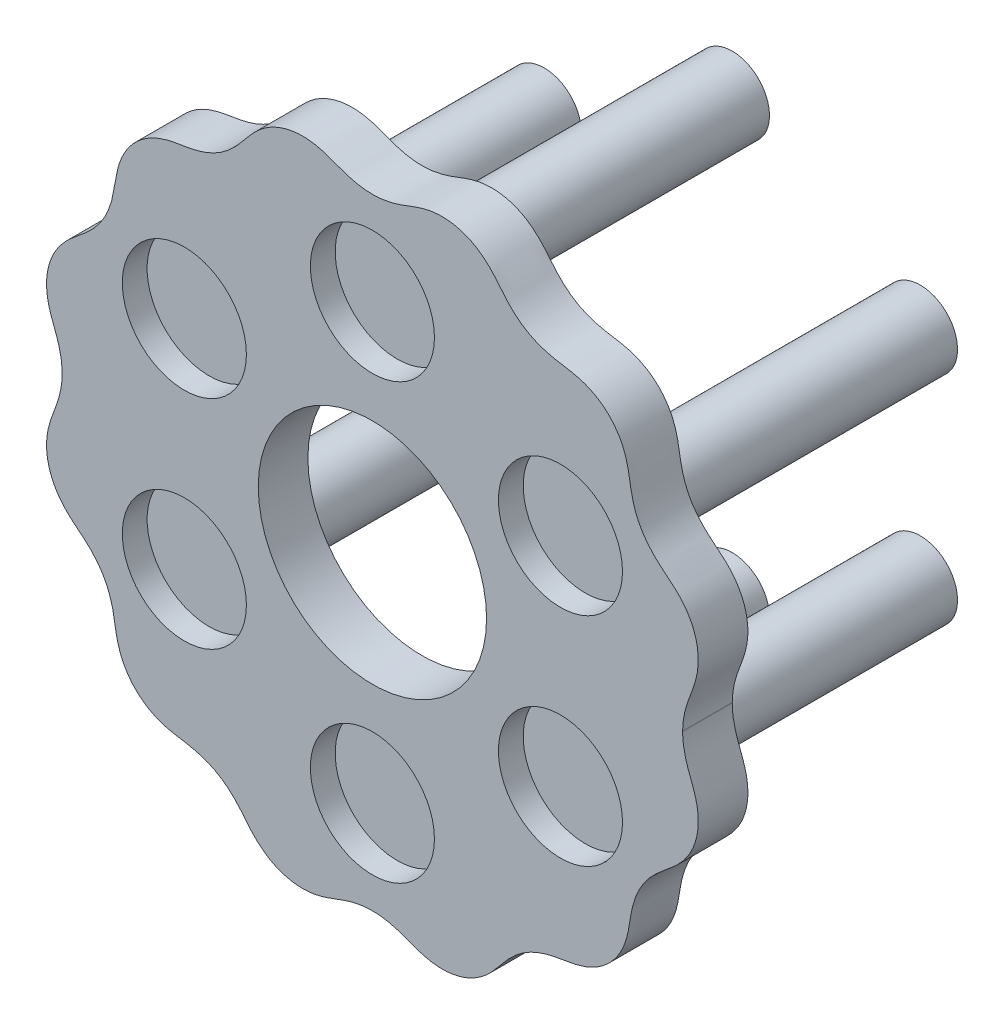
SolidWorks part; units mm, degrees
material "Polylactic Acid (PLA)"
ref_plane "Front Plane" through (0, 0, 0) normal (0, 0, 1) x (1, 0, 0)
ref_plane "Top Plane" through (0, 0, 0) normal (0, 1, 0) x (1, 0, 0)
ref_plane "Right Plane" through (0, 0, 0) normal (1, 0, 0) x (0, 0, -1)
sketch "Sketch3" plane through (0, 0, 0) normal (0, 0, 1) x (1, 0, 0)
  circle A0 centre (0, 0) radius 9.2
  circle A1 centre (0, 0) radius 17.5 construction
  circle A2 centre (0, 17.5) radius 5 construction
  circle A3 centre (15.1554, 8.75) radius 5 construction
  circle A4 centre (15.1554, -8.75) radius 5 construction
  circle A5 centre (0, -17.5) radius 5 construction
  circle A6 centre (-15.1554, -8.75) radius 5 construction
  circle A7 centre (-15.1554, 8.75) radius 5 construction
  spline S0 degree 4 poles (21.1908, 13.4898) (21.2856, 13.2293) (21.5047, 12.7166) (21.9256, 11.9944) (22.6531, 11.1441) (23.6487, 10.2926) (24.8547, 9.373) (25.8136, 8.0448) (26.2513, 6.5807) (26.291, 5.362) (26.1425, 4.3728) (25.9222, 3.637) (25.662, 2.971) (25.4535, 2.4089) (25.3271, 2.03) (25.2348, 1.7101) (25.1694, 1.4518) (25.1138, 1.1915) (25.0684, 0.9287) (25.0339, 0.6638) (25.0136, 0.4392) (25.0034, 0.2182) (24.9998, 0.0511) (24.9998, -0.0519) (25.0027, -0.1861) (25.0086, -0.3317) (25.0175, -0.4711) (25.0292, -0.6041) (25.0438, -0.7358) (25.0613, -0.8682) (25.0866, -1.0342) (25.1223, -1.2324) (25.1717, -1.4616) (25.2379, -1.7216) (25.3315, -2.0435) (25.4377, -2.3615) (25.5528, -2.6764) (25.6953, -3.0525) (25.8373, -3.4288) (26.0075, -3.9196) (26.1691, -4.5364) (26.293, -5.4006) (26.2489, -6.5093) (25.9006, -7.7589) (25.2509, -8.824) (24.5594, -9.5488) (23.8729, -10.1329) (23.242, -10.6335) (22.5405, -11.262) (21.8598, -12.0935) (21.3371, -13.0271) (20.9865, -14.0322) (20.7832, -15.0691) (20.6292, -16.2106) (20.2958, -17.4236) (19.6201, -18.6144) (18.5782, -19.6482) (17.3773, -20.3163) (16.1515, -20.64) (14.7399, -20.8265) (13.4394, -21.1259) (12.2371, -21.7311) (11.2173, -22.5863) (10.5105, -23.3824) (9.8039, -24.3012) (8.9125, -25.2023) (7.7314, -25.9117) (6.3093, -26.2999) (4.9316, -26.2885) (3.7061, -25.9646) (2.6337, -25.523) (1.6267, -25.1818) (0.5814, -24.9891) (-0.4789, -24.9807) (-1.521, -25.1546) (-2.5204, -25.4795) (-3.4192, -25.8479) (-4.2744, -26.1194) (-5.0841, -26.2552) (-5.8272, -26.2778) (-6.7511, -26.1767) (-7.8194, -25.8504) (-8.8645, -25.242) (-9.7745, -24.3376) (-10.489, -23.4094) (-11.1981, -22.6045) (-12.0193, -21.9108) (-12.9507, -21.3713) (-13.9612, -21.0044) (-15.0125, -20.7907) (-16.1735, -20.6366) (-17.4128, -20.3041) (-18.6216, -19.6172) (-19.5352, -18.6909) (-20.1095, -17.7445) (-20.4683, -16.8114) (-20.6693, -15.9295) (-20.8004, -14.9513) (-21.0215, -13.8975) (-21.3995, -12.8918) (-21.9457, -11.9715) (-22.6396, -11.1645) (-23.4354, -10.4692) (-24.3471, -9.7654) (-25.2322, -8.8715) (-25.9257, -7.6947) (-26.3017, -6.2829) (-26.2854, -4.917) (-25.9623, -3.7014) (-25.5242, -2.6362) (-25.1845, -1.6355) (-24.9896, -0.5891) (-24.9797, 0.481) (-25.1578, 1.5405) (-25.4952, 2.5629) (-25.8707, 3.4757) (-26.1355, 4.3406) (-26.2885, 5.3286) (-26.2611, 6.43) (-25.9336, 7.6784) (-25.2377, 8.8666) (-24.345, 9.7676) (-23.427, 10.4756) (-22.627, 11.1764) (-21.9369, 11.9843) (-21.3977, 12.8977) (-21.0267, 13.8865) (-20.8061, 14.9146) (-20.653, 16.0603) (-20.3956, 17.1161) (-19.9569, 18.0284) (-19.3001, 18.9288) (-18.4837, 19.6923) (-17.4358, 20.2946) (-16.1976, 20.6324) (-15.0368, 20.7873) (-13.9849, 20.9979) (-12.9731, 21.361) (-12.0395, 21.8966) (-11.2157, 22.5872) (-10.504, 23.3902) (-9.7903, 24.3186) (-8.8841, 25.2269) (-7.6859, 25.9322) (-6.4273, 26.2622) (-5.3206, 26.2881) (-4.3329, 26.1336) (-3.4683, 25.8679) (-2.5556, 25.4923) (-1.5328, 25.1559) (-0.4731, 24.979) (0.597, 24.9904) (1.6431, 25.1866) (2.6435, 25.5272) (3.7088, 25.9651) (4.9249, 26.2864) (6.2909, 26.3007) (7.702, 25.9226) (8.8779, 25.2273) (9.7704, 24.341) (10.4741, 23.4292) (11.1701, 22.634) (11.978, 21.941) (12.899, 21.3961) (13.9051, 21.0193) (14.9591, 20.7992) (15.9373, 20.6681) (16.819, 20.466) (17.7516, 20.1059) (18.6971, 19.5302) (19.6221, 18.6152) (20.3072, 17.4054) (20.6379, 16.1657) (20.7918, 15.0047) (21.0066, 13.9535) (21.3747, 12.9435) (21.9154, 12.0128) (22.6101, 11.1925) (23.4156, 10.4841) (24.3437, 9.7696) (25.2468, 8.858) (25.9409, 7.6621) (26.2625, 6.4138) (26.2848, 5.4123) (26.1914, 4.7043) (26.0881, 4.2266) (25.9672, 3.8023) (25.8079, 3.3457) (25.6196, 2.8553) (25.4588, 2.4245) (25.3339, 2.0507) (25.2417, 1.7354) (25.1764, 1.4809) (25.1203, 1.2244) (25.0741, 0.9651) (25.0385, 0.7047) (25.017, 0.4825) (25.0053, 0.2643) (25.0004, 0.1004) (24.9996, -0.0012) (25.0018, -0.1656) (25.01, -0.3844) (25.028, -0.6072) (25.0597, -0.8689) (25.1021, -1.1294) (25.1679, -1.4517) (25.266, -1.8346) (25.4047, -2.2742) (25.5863, -2.7686) (25.7756, -3.26) (25.9402, -3.7196) (26.0686, -4.1508) (26.1813, -4.6424) (26.2599, -5.1966) (26.2771, -5.8503) (26.1868, -6.6388) (25.9656, -7.4497) (25.5952, -8.2566) (25.0637, -9.0243) (24.3767, -9.7304) (23.5662, -10.3704) (22.7327, -11.0654) (21.9759, -11.9212) (21.5356, -12.6558) (21.307, -13.1772) (21.208, -13.4432) knots 0 0 0 0 0 0.005467 0.010935 0.016402 0.021869 0.031276 0.040682 0.047884 0.051484 0.055085 0.060328 0.062949 0.065571 0.066882 0.068192 0.069503 0.070814 0.072125 0.073435 0.074746 0.075401 0.076057 0.076717 0.077377 0.078036 0.078696 0.079356 0.080016 0.080676 0.081336 0.082656 0.083975 0.085295 0.086615 0.089254 0.090574 0.091894 0.094534 0.097173 0.100798 0.104424 0.111675 0.118848 0.126022 0.128665 0.131308 0.136594 0.14188 0.147166 0.152358 0.157549 0.16274 0.167931 0.175042 0.182153 0.189327 0.1965 0.201723 0.206946 0.217392 0.222615 0.227838 0.233061 0.238284 0.245457 0.252631 0.259805 0.266978 0.272201 0.277424 0.282647 0.287869 0.29303 0.29819 0.30335 0.30851 0.31216 0.31581 0.319459 0.323109 0.330383 0.337658 0.342925 0.348192 0.35346 0.358727 0.363994 0.369262 0.374529 0.379796 0.387071 0.394345 0.401519 0.405106 0.408692 0.413978 0.419265 0.424551 0.429837 0.435028 0.440219 0.44541 0.450602 0.457712 0.464823 0.471934 0.479045 0.484236 0.489427 0.494619 0.49981 0.505096 0.510382 0.515668 0.520954 0.524541 0.528128 0.535301 0.542475 0.549649 0.554872 0.560094 0.565317 0.57054 0.5757 0.58086 0.58602 0.591181 0.59848 0.60213 0.605779 0.613054 0.620328 0.625595 0.630863 0.63613 0.641397 0.646665 0.651932 0.657199 0.662467 0.669741 0.677015 0.684189 0.687776 0.691363 0.696649 0.701935 0.707221 0.712507 0.717698 0.722889 0.728081 0.733272 0.740383 0.747494 0.754604 0.761715 0.766906 0.772098 0.777289 0.78248 0.787766 0.793052 0.798338 0.803624 0.807211 0.810798 0.817972 0.825246 0.83252 0.837788 0.843055 0.848322 0.85359 0.858857 0.864124 0.869392 0.874659 0.881933 0.889208 0.896232 0.899744 0.9015 0.903256 0.905842 0.908428 0.911014 0.9136 0.914893 0.916186 0.917479 0.918772 0.920065 0.921358 0.922651 0.923297 0.923944 0.924592 0.92524 0.926536 0.927831 0.929127 0.930423 0.931719 0.934311 0.936903 0.939495 0.942087 0.944679 0.946512 0.948345 0.952012 0.955678 0.959345 0.963918 0.968492 0.973065 0.977639 0.983229 0.988819 0.99441 1 1 1 1 1 construction
  spline S1 degree 4 poles (25, 0) (25, -0.0284) (25.0005, -0.0852) (25.0027, -0.1861) (25.0086, -0.3317) (25.0175, -0.4711) (25.0292, -0.6041) (25.0438, -0.7358) (25.0613, -0.8682) (25.0866, -1.0342) (25.1223, -1.2324) (25.1717, -1.4616) (25.2379, -1.7216) (25.3315, -2.0435) (25.4377, -2.3615) (25.5528, -2.6764) (25.6953, -3.0525) (25.8373, -3.4288) (26.0075, -3.9196) (26.1691, -4.5364) (26.293, -5.4006) (26.2489, -6.5093) (25.9006, -7.7589) (25.2509, -8.824) (24.5594, -9.5488) (23.8729, -10.1329) (23.242, -10.6335) (22.5405, -11.262) (21.8598, -12.0935) (21.3371, -13.0271) (20.9865, -14.0322) (20.7832, -15.0691) (20.6292, -16.2106) (20.2958, -17.4236) (19.6201, -18.6144) (18.5782, -19.6482) (17.3773, -20.3163) (16.1515, -20.64) (14.7399, -20.8265) (13.4394, -21.1259) (12.2371, -21.7311) (11.2173, -22.5863) (10.5105, -23.3824) (9.8039, -24.3012) (8.9125, -25.2023) (7.7314, -25.9117) (6.3093, -26.2999) (4.9316, -26.2885) (3.7061, -25.9646) (2.6337, -25.523) (1.6267, -25.1818) (0.5814, -24.9891) (-0.4789, -24.9807) (-1.521, -25.1546) (-2.5204, -25.4795) (-3.4192, -25.8479) (-4.2744, -26.1194) (-5.0841, -26.2552) (-5.8272, -26.2778) (-6.7511, -26.1767) (-7.8194, -25.8504) (-8.8645, -25.242) (-9.7745, -24.3376) (-10.489, -23.4094) (-11.1981, -22.6045) (-12.0193, -21.9108) (-12.9507, -21.3713) (-13.9612, -21.0044) (-15.0125, -20.7907) (-16.1735, -20.6366) (-17.4128, -20.3041) (-18.6216, -19.6172) (-19.5352, -18.6909) (-20.1095, -17.7445) (-20.4683, -16.8114) (-20.6693, -15.9295) (-20.8004, -14.9513) (-21.0215, -13.8975) (-21.3995, -12.8918) (-21.9457, -11.9715) (-22.6396, -11.1645) (-23.4354, -10.4692) (-24.3471, -9.7654) (-25.2322, -8.8715) (-25.9257, -7.6947) (-26.3017, -6.2829) (-26.2854, -4.917) (-25.9623, -3.7014) (-25.5242, -2.6362) (-25.1845, -1.6355) (-24.9896, -0.5891) (-24.9797, 0.481) (-25.1578, 1.5405) (-25.4952, 2.5629) (-25.8707, 3.4757) (-26.1355, 4.3406) (-26.2885, 5.3286) (-26.2611, 6.43) (-25.9336, 7.6784) (-25.2377, 8.8666) (-24.345, 9.7676) (-23.427, 10.4756) (-22.627, 11.1764) (-21.9369, 11.9843) (-21.3977, 12.8977) (-21.0267, 13.8865) (-20.8061, 14.9146) (-20.653, 16.0603) (-20.3956, 17.1161) (-19.9569, 18.0284) (-19.3001, 18.9288) (-18.4837, 19.6923) (-17.4358, 20.2946) (-16.1976, 20.6324) (-15.0368, 20.7873) (-13.9849, 20.9979) (-12.9731, 21.361) (-12.0395, 21.8966) (-11.2157, 22.5872) (-10.504, 23.3902) (-9.7903, 24.3186) (-8.8841, 25.2269) (-7.6859, 25.9322) (-6.4273, 26.2622) (-5.3206, 26.2881) (-4.3329, 26.1336) (-3.4683, 25.8679) (-2.5556, 25.4923) (-1.5328, 25.1559) (-0.4731, 24.979) (0.597, 24.9904) (1.6431, 25.1866) (2.6435, 25.5272) (3.7088, 25.9651) (4.9249, 26.2864) (6.2909, 26.3007) (7.702, 25.9226) (8.8779, 25.2273) (9.7704, 24.341) (10.4741, 23.4292) (11.1701, 22.634) (11.978, 21.941) (12.899, 21.3961) (13.9051, 21.0193) (14.9591, 20.7992) (15.9373, 20.6681) (16.819, 20.466) (17.7516, 20.1059) (18.6971, 19.5302) (19.6221, 18.6152) (20.3072, 17.4054) (20.6379, 16.1657) (20.7918, 15.0047) (21.0066, 13.9535) (21.3747, 12.9435) (21.9154, 12.0128) (22.6101, 11.1925) (23.4156, 10.4841) (24.3437, 9.7696) (25.2468, 8.858) (25.9409, 7.6621) (26.2625, 6.4138) (26.2848, 5.4123) (26.1914, 4.7043) (26.0881, 4.2266) (25.9672, 3.8023) (25.8079, 3.3457) (25.6196, 2.8553) (25.4588, 2.4245) (25.3339, 2.0507) (25.2417, 1.7354) (25.1764, 1.4809) (25.1203, 1.2244) (25.0741, 0.9651) (25.0385, 0.7047) (25.017, 0.4825) (25.0053, 0.2643) (25.0014, 0.1332) (25.0004, 0.0775) (25.0002, 0.0497) knots 0.076057 0.076057 0.076057 0.076057 0.076057 0.076717 0.077377 0.078036 0.078696 0.079356 0.080016 0.080676 0.081336 0.082656 0.083975 0.085295 0.086615 0.089254 0.090574 0.091894 0.094534 0.097173 0.100798 0.104424 0.111675 0.118848 0.126022 0.128665 0.131308 0.136594 0.14188 0.147166 0.152358 0.157549 0.16274 0.167931 0.175042 0.182153 0.189327 0.1965 0.201723 0.206946 0.217392 0.222615 0.227838 0.233061 0.238284 0.245457 0.252631 0.259805 0.266978 0.272201 0.277424 0.282647 0.287869 0.29303 0.29819 0.30335 0.30851 0.31216 0.31581 0.319459 0.323109 0.330383 0.337658 0.342925 0.348192 0.35346 0.358727 0.363994 0.369262 0.374529 0.379796 0.387071 0.394345 0.401519 0.405106 0.408692 0.413978 0.419265 0.424551 0.429837 0.435028 0.440219 0.44541 0.450602 0.457712 0.464823 0.471934 0.479045 0.484236 0.489427 0.494619 0.49981 0.505096 0.510382 0.515668 0.520954 0.524541 0.528128 0.535301 0.542475 0.549649 0.554872 0.560094 0.565317 0.57054 0.5757 0.58086 0.58602 0.591181 0.59848 0.60213 0.605779 0.613054 0.620328 0.625595 0.630863 0.63613 0.641397 0.646665 0.651932 0.657199 0.662467 0.669741 0.677015 0.684189 0.687776 0.691363 0.696649 0.701935 0.707221 0.712507 0.717698 0.722889 0.728081 0.733272 0.740383 0.747494 0.754604 0.761715 0.766906 0.772098 0.777289 0.78248 0.787766 0.793052 0.798338 0.803624 0.807211 0.810798 0.817972 0.825246 0.83252 0.837788 0.843055 0.848322 0.85359 0.858857 0.864124 0.869392 0.874659 0.881933 0.889208 0.896232 0.899744 0.9015 0.903256 0.905842 0.908428 0.911014 0.9136 0.914893 0.916186 0.917479 0.918772 0.920065 0.921358 0.922651 0.923297 0.923944 0.923944 0.923944 0.923944 0.923944
  spline S2 degree 1 poles (25.0002, 0.0497) (25, 0) knots 0 0 1 1
  point P17 (0, 0)
  dimension "D1" = 18.4
  dimension "D2" = 35
  dimension "D3" = 10
  dimension "D4" = 6
extrude "Boss-Extrude2" add sketch "Sketch3" along normal blind 4
sketch "Sketch6" plane through (0, 0, 4) normal (0, 0, 1) x (1, 0, 0)
  circle A0 centre (15.1554, -8.75) radius 5 construction
  circle A1 centre (0, -17.5) radius 5 construction
  circle A2 centre (-15.1554, -8.75) radius 5 construction
  circle A3 centre (0, 0) radius 17.5 construction
  circle A4 centre (15.1554, 8.75) radius 5 construction
  circle A5 centre (0, 17.5) radius 5 construction
  circle A6 centre (15.1554, -8.75) radius 5
  circle A7 centre (0, -17.5) radius 5
  circle A8 centre (-15.1554, -8.75) radius 5
  circle A9 centre (0, 0) radius 17.5 construction
  circle A10 centre (15.1554, 8.75) radius 5
  circle A11 centre (0, 17.5) radius 5
  circle A12 centre (-15.1554, 8.75) radius 5 construction
  circle A13 centre (-15.1554, 8.75) radius 5
sketch "Sketch7" plane through (0, 0, 0) normal (0, 0, -1) x (-1, 0, 0)
  circle A0 centre (0, 17.5) radius 3
  circle A1 centre (15.1554, 8.75) radius 3
  circle A2 centre (15.1554, -8.75) radius 3
  circle A3 centre (0, -17.5) radius 3
  circle A4 centre (-15.1554, -8.75) radius 3
  circle A5 centre (-15.1554, 8.75) radius 3
  point P15 (0, 0)
  dimension "D1" = 6
  dimension "D3" = 9.8446
  dimension "D2" = 6
extrude "Boss-Extrude3" add sketch "Sketch7" along normal blind 25
extrude "Cut-Extrude2" cut sketch "Sketch6" against normal blind 2
